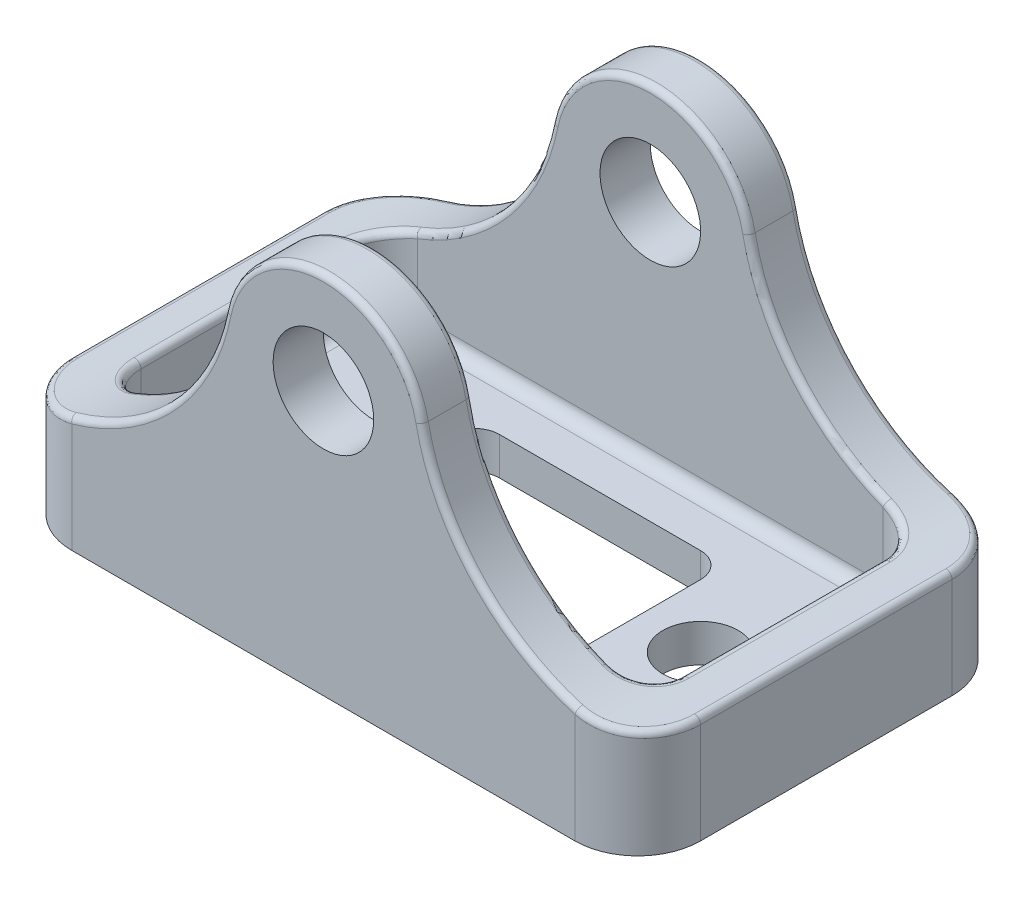
SolidWorks part; units mm, degrees
material "7075-T6, Płyta (SS)"
ref_plane "Płaszczyzna XY" through (0, 0, 0) normal (0, 0, 1) x (1, 0, 0)
ref_plane "Płaszczyzna XZ" through (0, 0, 0) normal (0, 1, 0) x (1, 0, 0)
ref_plane "Płaszczyzna YZ" through (0, 0, 0) normal (1, 0, 0) x (0, 0, -1)
sketch "Szkic1" plane through (0, 0, 0) normal (0, 0, 1) x (1, 0, 0)
  line L0 (0, 0) -> (0, 56.7859) construction
  line L1 (-25, 29) -> (25, 29)
  line L2 (-25, 29) -> (-25, 0)
  line L3 (-25, 0) -> (25, 0)
  line L4 (25, 29) -> (25, 0)
  circle A0 centre (0, 21) radius 4
  point P4 (0, 0)
  dimension "D2" = 8
  dimension "D1" = 29
  dimension "D3" = 50
  dimension "D4" = 8
extrude "Dodanie-wyciągnięcie1" add sketch "Szkic1" along normal blind 30
sketch "Szkic3" plane through (0, 0, 0) normal (0, -1, 0) x (1, 0, 0)
  line L0 (0, 0) -> (0, 32.1886) construction
  line L1 (-25, 15) -> (25, 15) construction
  line L2 (-25, 30) -> (-25, 0) construction
  line L3 (25, 30) -> (25, 0) construction
  circle A0 centre (-15, 15) radius 3
  circle A1 centre (15, 15) radius 3
  dimension "D1" = 6
  dimension "D2" = 6
  dimension "D3" = 30
  dimension "D4" = 15
extrude "Wytnij-wyciągnięcie1" cut sketch "Szkic3" against normal through all
sketch "Szkic4" plane through (0, 0, 0) normal (0, -1, 0) x (1, 0, 0)
  line L0 (-25, 30) -> (25, 30) construction
  line L4 (25, 25) -> (25, 0) construction
  line L5 (-25, 0) -> (25, 0) construction
  line L6 (-25, 25) -> (-25, 0) construction
  line L8 (-21.5, 26) -> (21.5, 26)
  line L16 (21.5, 26) -> (-21.5, 26)
  line L17 (-21.5, 26) -> (-21.5, 4)
  line L18 (-21.5, 4) -> (21.5, 4)
  line L19 (21.5, 4) -> (21.5, 26)
  line L24 (-25, 0) -> (25, 0)
  line L25 (25, 0) -> (25, 30)
  line L26 (25, 30) -> (-25, 30)
  line L27 (-25, 30) -> (-25, 0)
  point P3 (-27, 27)
  point P5 (27, 27)
  point P6 (25, 15)
  dimension "D2" = 4
  dimension "D1" = 4
  dimension "D3" = 3.5
  dimension "D4" = 3.5
extrude "Wytnij-wyciągnięcie2" cut sketch "Szkic4" against normal through all from offset 3 offset against normal yes
sketch "Szkic5" plane through (0, 0, 30) normal (0, 0, 1) x (1, 0, 0)
  line L0 (0, 0) -> (0, 61.5463) construction
  line L1 (25, 0) -> (25, 29) construction
  line L2 (-25, 8.5049) -> (-25, 29)
  line L3 (-25, 29) -> (25, 29)
  line L4 (25, 29) -> (25, 8.5049)
  line L5 (-25, 29) -> (-25, 0) construction
  arc A0 (7.8446, 22.5689) -> (-7.8446, 22.5689) centre (0, 21) ccw
  arc A1 (-25, 8.5049) -> (-7.8446, 22.5689) centre (-25, 26) ccw
  arc A2 (7.8446, 22.5689) -> (25, 8.5049) centre (25, 26) ccw
  line M2 (-25, 29) -> (-25, 0)
  line M4 (25, 0) -> (25, 29)
  line M5 (25, 29) -> (-25, 29)
  dimension "D1" = 16
  dimension "D2" = 3
  dimension "D3" = 3
extrude "Wytnij-wyciągnięcie3" cut sketch "Szkic5" against normal through all both and the other way through all contours A1 A0 L3 M2 | A0 A2 M4 M5
fillet "Zaokrąglenie1" radius 1 4 edges at (0, 3, 26) (-21.5, 3, 15) (0, 3, 4) (21.5, 3, 15)
sketch "Szkic6" plane through (0, 3, 0) normal (0, 1, 0) x (1, 0, 0)
  line L1 (8, -22) -> (-8, -22)
  line L2 (10, -20) -> (10, -10)
  line L3 (8, -8) -> (-8, -8)
  line L4 (-10, -20) -> (-10, -10)
  line L6 (-25, 0) -> (25, 0) construction
  line L8 (-25, -30) -> (25, -30) construction
  circle A0 centre (15, -15) radius 3 construction
  circle A1 centre (-15, -15) radius 3 construction
  arc A2 (-8, -22) -> (-10, -20) centre (-8, -20) cw
  arc A3 (-10, -10) -> (-8, -8) centre (-8, -10) cw
  arc A4 (8, -8) -> (10, -10) centre (8, -10) cw
  arc A5 (10, -20) -> (8, -22) centre (8, -20) cw
  dimension "D5" = 2
  dimension "D1" = 5
  dimension "D2" = 5
  dimension "D3" = 8
  dimension "D4" = 8
extrude "Wytnij-wyciągnięcie4" cut sketch "Szkic6" against normal blind 10
fillet "Zaokrąglenie2" radius 3 8 edges at (-21.5, 6.4293, 26) (-21.5, 6.4293, 4) (21.5, 6.4293, 4) (21.5, 6.4293, 26) (21.2071, 3.2929, 25.7071) (21.2071, 3.2929, 4.2929) (-21.2071, 3.2929, 4.2929) (-21.2071, 3.2929, 25.7071)
fillet "Zaokrąglenie3" radius 5 4 edges at (25, 4.2525, 0) (-25, 4.2525, 0)
fillet "Zaokrąglenie4" radius 0.5 24 edges at (-23.906, 8.5391, 28.1214) (-23.0663, 8.6121, 1.0506) (-12.0707, 14.2139, 0) (0, 29, 0) (12.0707, 14.2139, 0) (23.906, 8.5391, 1.8786) (23.0663, 8.6121, 28.9494) (20.8705, 8.9992, 24.8387) (21.5, 8.8586, 15) (20.4247, 9.1138, 4.6988) (11.549, 14.813, 4) (0, 29, 4) (-11.549, 14.813, 4) (-20.8705, 8.9992, 5.1613) (-21.5, 8.8586, 15) (-20.4247, 9.1138, 25.3012) (-11.549, 14.813, 26) (0, 29, 26) (11.549, 14.813, 26)
sketch "Szkic7" plane through (0, 0, 30) normal (0, 0, 1) x (1, 0, 0)
  circle A0 centre (0, 21) radius 6.5
  dimension "D1" = 13
extrude "Dodanie-wyciągnięcie2" [suppressed] add sketch "Szkic7" against normal up to surface (30 mm away)
